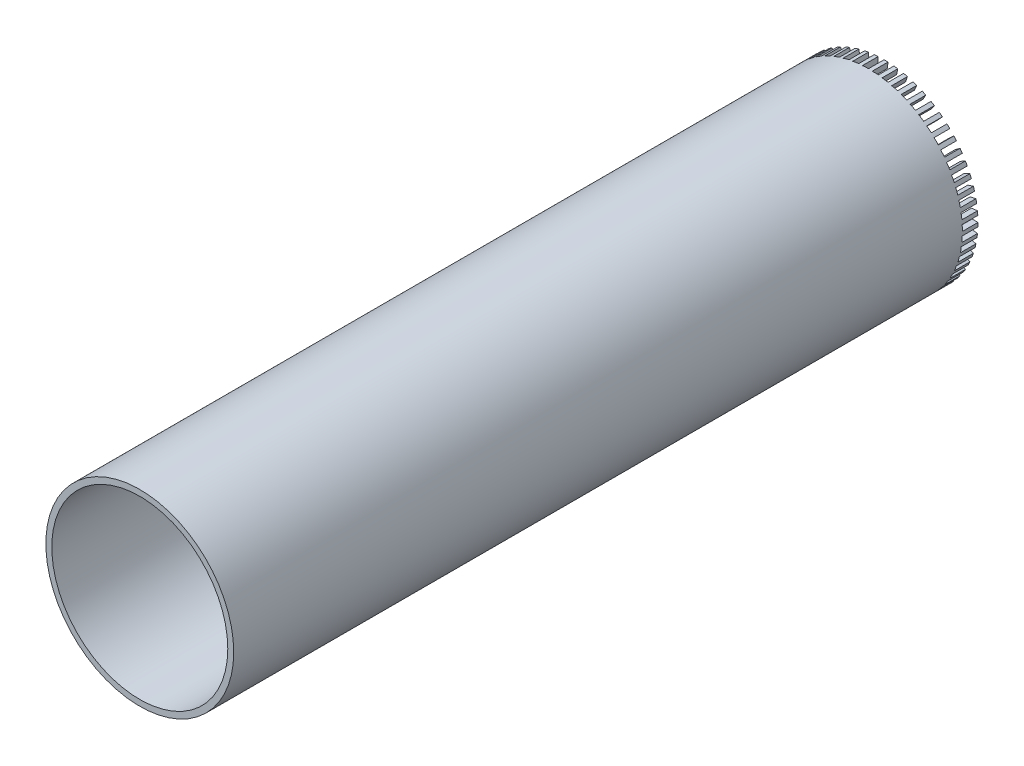
SolidWorks part; units mm, degrees
other "Markup1"
sketch "Sketch12" plane through (-23.8535, 23.8535, -0.1502) normal (-0.8314, 0.5534, -0.05) x (0.5439, 0.8289, 0.1304)
sketch "Sketch13" plane through (-23.8535, 23.8535, 0) normal (-0.8314, 0.5534, -0.05) x (0.5439, 0.8289, 0.1304)
sketch "Sketch14" plane through (-23.8535, 23.8535, 0) normal (-0.8314, 0.5534, -0.05) x (0.5439, 0.8289, 0.1304)
sketch "Sketch15" plane through (-23.8535, 23.8535, 0) normal (-0.8314, 0.5534, -0.05) x (0.5439, 0.8289, 0.1304)
ref_plane "Front Plane" through (0, 0, 0) normal (0, 0, 1) x (1, 0, 0)
ref_plane "Top Plane" through (0, 0, 0) normal (0, 1, 0) x (1, 0, 0)
ref_plane "Right Plane" through (0, 0, 0) normal (1, 0, 0) x (0, 0, -1)
sketch "Sketch1" plane through (0, 0, 0) normal (0, 0, 1) x (1, 0, 0)
  circle A0 centre (0, 0) radius 23.8535
  circle A1 centre (0, 0) radius 22.35
  dimension "D1" = 47.707
  dimension "D2" = 44.7
extrude "Boss-Extrude4" add sketch "Sketch1" along normal blind 189
sketch "Sketch5" plane through (0, 0, 0) normal (0, 1, 0) x (1, 0, 0)
  line L0 (0, 0) -> (0, -90.6847) construction
  line L2 (0, 0) -> (-1.5, 0)
  line L3 (0, 0) -> (0, -3.95)
  line L4 (0, -3.95) -> (-1.5, -3.95)
  line L5 (-1.5, 0) -> (-1.5, -3.95)
  dimension "Ltod" = 3.95
  dimension "slit width" = 1.5
extrude "Cut-Extrude2" cut sketch "Sketch5" against normal blind 10 and the other way through all
ref_axis "Axis1" through (0, 0, 189) along (0, 0, -1)
pattern_circular "CirPattern1" count 60 over 360 about axis through (0, 0, 189) along (0, 0, -1) of "Cut-Extrude2"
sketch "Sketch7" plane through (0, 0, 0) normal (1, 0, 0) x (0, 0, -1)
  line L0 (-3.95, 23.8535) -> (-12.8141, 16.4202)
  line L1 (-12.8141, 16.4202) -> (-1.5373, 12.6305)
  line L2 (-1.5373, 12.6305) -> (0.329, 12.0033)
  line L3 (0.329, 12.0033) -> (-3.95, 23.8535)
extrude "Cut-Extrude3" cut sketch "Sketch7" against normal blind 1.5
pattern_circular "CirPattern6" count 60 over 360 about axis through (0, 0, 189) along (0, 0, -1) of "Cut-Extrude3"
sketch "Sketch11" plane through (0, 0, 0) normal (-0.9945, 0.1045, 0) x (0, 0, 1)
  line L0 (0, 23.8535) -> (0.8938, 23.1035)
  line L1 (5.7429, 22.35) -> (0, 22.35) construction
  line L2 (0.8938, 23.1035) -> (-0.1502, 22.8836)
  line L3 (-0.1502, 22.8836) -> (0, 23.8535)
  dimension "D1" = 1.1668
equation "\"Dt\"= 0.047707m"
equation "\"wall thick\"= 0.001500m"
equation "\"length\"= 0.1890m"
equation "\"slit width@Sketch5\" = 0.0015m"
equation "\"tpg\"= 0.00985m"
